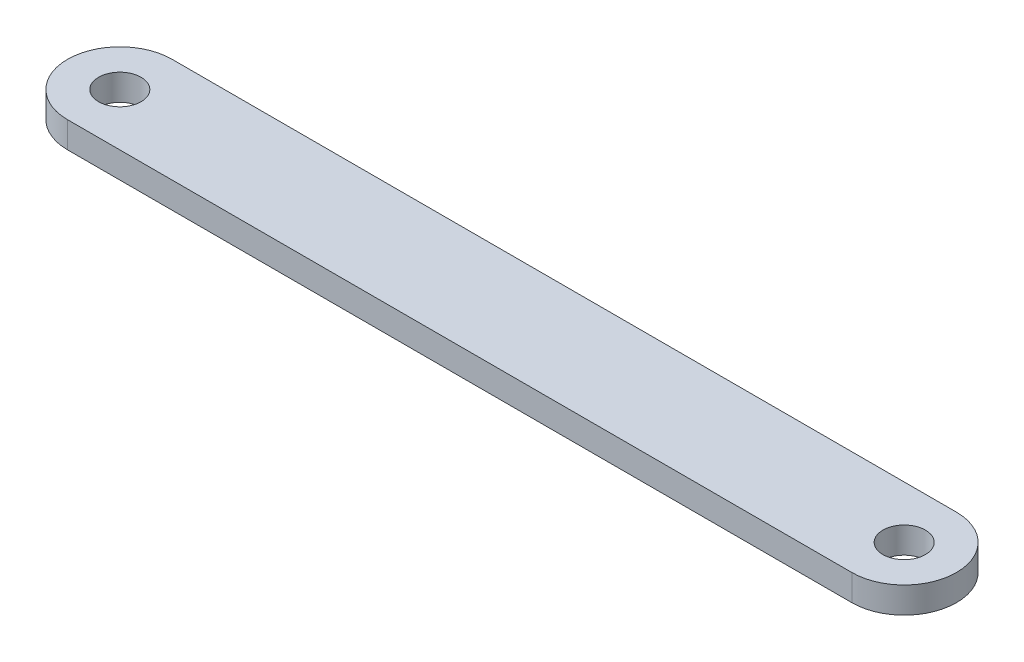
SolidWorks part; units mm, degrees
ref_plane "Front Plane" through (0, 0, 0) normal (0, 0, 1) x (1, 0, 0)
ref_plane "Top Plane" through (0, 0, 0) normal (0, 1, 0) x (1, 0, 0)
ref_plane "Right Plane" through (0, 0, 0) normal (1, 0, 0) x (0, 0, -1)
sketch "Sketch1" plane through (0, 0, 0) normal (0, 1, 0) x (1, 0, 0)
  line L0 (-47.625, 0) -> (47.625, 0) construction
  line L1 (-47.625, 6.35) -> (47.625, 6.35)
  line L2 (-47.625, -6.35) -> (47.625, -6.35)
  arc A0 (-47.625, 6.35) -> (-47.625, -6.35) centre (-47.625, 0) ccw
  arc A1 (47.625, -6.35) -> (47.625, 6.35) centre (47.625, 0) ccw
  circle A2 centre (47.625, 0) radius 2.5797
  circle A3 centre (-47.625, 0) radius 2.5797
  point P3 (0, 0)
  dimension "D2" = 6.35
  dimension "D3" = 5.1594
  dimension "D1" = 95.25
extrude "Boss-Extrude1" add sketch "Sketch1" along normal blind 3.175
